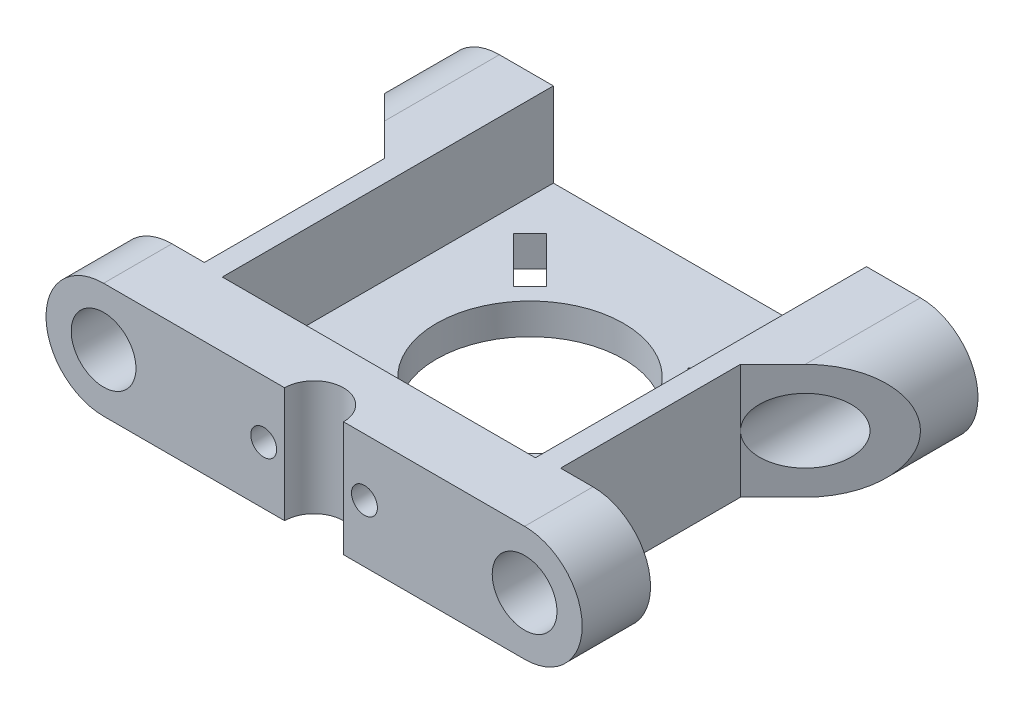
SolidWorks part; units mm, degrees
ref_plane "Piano frontale" through (0, 0, 0) normal (0, 0, 1) x (1, 0, 0)
ref_plane "Piano superiore" through (0, 0, 0) normal (0, 1, 0) x (1, 0, 0)
ref_plane "Piano destro" through (0, 0, 0) normal (1, 0, 0) x (0, 0, -1)
sketch "Schizzo1" plane through (0, 0, 0) normal (0, 0, 1) x (1, 0, 0)
  line L0 (-29.25, 0) -> (29.25, 0) construction
  line L1 (-29.25, -8) -> (29.25, -8)
  line L2 (0, 8) -> (0, -8) construction
  line L3 (-29.25, 8) -> (29.25, 8)
  arc A0 (-29.25, 8) -> (-29.25, -8) centre (-29.25, 0) ccw
  circle A1 centre (-29.25, 0) radius 4.5
  circle A2 centre (29.25, 0) radius 4.5
  arc A3 (29.25, 8) -> (29.25, -8) centre (29.25, 0) cw
  point P4 (0, 0)
  dimension "D2" = 16
  dimension "D3" = 9
  dimension "D1" = 29.25
extrude "Base" add sketch "Schizzo1" along normal mid plane 55
sketch "Schizzo3" plane through (0, 8, 0) normal (0, 1, 0) x (1, 0, 0)
  line L0 (13, 2.5) -> (-13, 2.5) construction
  line L1 (16.1927, 20.9555) -> (12.0915, 12.3288) construction
  line L2 (9.8288, 14.5915) -> (18.4555, 18.6927) construction
  line L3 (12.0915, 12.3288) -> (18.4555, 18.6927)
  line L4 (16.1927, 20.9555) -> (18.4555, 18.6927)
  line L5 (9.8288, 14.5915) -> (12.0915, 12.3288)
  line L6 (9.8288, 14.5915) -> (16.1927, 20.9555)
  line L7 (9.8288, -9.5915) -> (18.4555, -13.6927) construction
  line L8 (37.25, -27.5) -> (37.25, -18)
  line L9 (37.25, -27.5) -> (37.25, 27.5) construction
  line L10 (37.25, -18) -> (24.75, -18)
  line L11 (24.75, -18) -> (24.75, 7)
  line L12 (24.75, -27.5) -> (24.75, -18) construction
  line L13 (24.75, 7) -> (37.25, 19.5)
  line L14 (37.25, 19.5) -> (37.25, -18)
  line L15 (16.1927, -15.9555) -> (12.0915, -7.3288) construction
  line L16 (0, 27.5) -> (0, -27.5) construction
  line L17 (29.25, 27.5) -> (-29.25, 27.5) construction
  line L18 (29.25, -27.5) -> (-29.25, -27.5) construction
  line L19 (-37.25, 19.5) -> (-37.25, -18)
  line L20 (-24.75, 7) -> (-37.25, 19.5)
  line L21 (-24.75, -18) -> (-24.75, 7)
  line L22 (-37.25, -18) -> (-24.75, -18)
  line L23 (-37.25, -27.5) -> (-37.25, -18)
  line L24 (0, 2.5) -> (-14.1421, 16.6421) construction
  line L25 (-9.8288, 14.5915) -> (-16.1927, 20.9555)
  line L26 (-9.8288, 14.5915) -> (-12.0915, 12.3288)
  line L27 (-16.1927, 20.9555) -> (-18.4555, 18.6927)
  line L28 (-12.0915, 12.3288) -> (-18.4555, 18.6927)
  line L29 (-9.8288, 14.5915) -> (-18.4555, 18.6927) construction
  line L30 (-16.1927, 20.9555) -> (-12.0915, 12.3288) construction
  line L31 (9.8288, -9.5915) -> (16.1927, -15.9555)
  line L32 (9.8288, -9.5915) -> (12.0915, -7.3288)
  line L33 (16.1927, -15.9555) -> (18.4555, -13.6927)
  line L34 (12.0915, -7.3288) -> (18.4555, -13.6927)
  line L35 (-16.1927, -15.9555) -> (-12.0915, -7.3288) construction
  line L36 (-9.8288, -9.5915) -> (-18.4555, -13.6927) construction
  line L37 (-12.0915, -7.3288) -> (-18.4555, -13.6927)
  line L38 (-16.1927, -15.9555) -> (-18.4555, -13.6927)
  line L39 (-9.8288, -9.5915) -> (-12.0915, -7.3288)
  line L40 (-9.8288, -9.5915) -> (-16.1927, -15.9555)
  line L41 (24.75, -27.5) -> (33.75, -27.5) construction
  line L42 (24.75, -27.5) -> (33.75, -27.5)
  line L43 (4.09, -27.5) -> (-4.09, -27.5)
  circle A0 centre (0, 2.5) radius 13
  arc A1 (-4.09, -27.5) -> (4.09, -27.5) centre (0, -27.5) cw
  point P26 (0, 2.5)
  line M14 (-29.25, -27.5) -> (29.25, -27.5)
  line M15 (29.25, -27.5) -> (29.25, 27.5)
  dimension "D4" = 26
  dimension "D1" = 9.5
  dimension "D2" = 25
  dimension "D3" = 135
  dimension "D5" = 45
  dimension "D6" = 3.2
  dimension "D7" = 9
  dimension "D8" = 15.5
  dimension "D9" = 25
  dimension "D10" = 8.18
extrude "Holes" cut sketch "Schizzo3" against normal through all contours L13 L11 L10 M15 | L14 L13 L10 M15 | A0 | A1 M14 | L3 L4 L6 L5 | L25 L27 L28 L26 | L22 L21 L20 L19 | L40 L38 L37 L39 | L31 L33 L34 L32 region at (0, 8, 25.7642) region at (33.4092, 8, 1.1704) region at (27.0619, 8, 4.344) region at (0, 8, -2.5)
sketch "Schizzo5" plane through (0, 8, 0) normal (0, 1, 0) x (1, 0, 0)
  line L0 (21.75, 27.5) -> (21.75, -18.5)
  line L1 (29.25, 27.5) -> (-29.25, 27.5) construction
  line L2 (21.75, -18.5) -> (-21.75, -18.5)
  line L3 (-21.75, -18.5) -> (-21.75, 27.5)
  line L4 (-21.75, 0) -> (21.75, 0) construction
  line L5 (-24.75, -18) -> (-24.75, 7) construction
  line L6 (29.25, -27.5) -> (4.09, -27.5) construction
  line L7 (21.75, 27.5) -> (-21.75, 27.5)
  point P10 (0, 0)
  dimension "D1" = 3
  dimension "D2" = 9
extrude "Flange" cut sketch "Schizzo5" against normal blind 11.7
sketch "Schizzo6" plane through (0, 0, 27.5) normal (0, 0, 1) x (1, 0, 0)
  line L0 (0, -8) -> (0, 8) construction
  line L3 (4.09, -8) -> (-4.09, -8) construction
  line L4 (4.09, 8) -> (-4.09, 8) construction
  line L5 (-37.25, 0) -> (37.25, 0) construction
  arc A0 (-29.25, 8) -> (-29.25, -8) centre (-29.25, 0) ccw construction
  arc A1 (29.25, -8) -> (29.25, 8) centre (29.25, 0) ccw construction
  circle A2 centre (7, 0) radius 1.8
  circle A3 centre (-7, 0) radius 1.8
  dimension "D1" = 3.6
  dimension "D2" = 7
extrude "Screw holes" cut sketch "Schizzo6" against normal up to next
sketch "Schizzo7" plane through (0, 0, 18.5) normal (0, 0, -1) x (-1, 0, 0)
  line L1 (-3.6, 0) -> (-5.3, 2.9445)
  line L2 (-5.3, 2.9445) -> (-8.7, 2.9445)
  line L3 (-8.7, 2.9445) -> (-10.4, 0)
  line L4 (-10.4, 0) -> (-8.7, -2.9445)
  line L5 (-8.7, -2.9445) -> (-5.3, -2.9445)
  line L6 (-5.3, -2.9445) -> (-3.6, 0)
  line L7 (10.4, 0) -> (8.7, 2.9445)
  line L8 (8.7, 2.9445) -> (5.3, 2.9445)
  line L9 (5.3, 2.9445) -> (3.6, 0)
  line L10 (3.6, 0) -> (5.3, -2.9445)
  line L11 (5.3, -2.9445) -> (8.7, -2.9445)
  line L12 (8.7, -2.9445) -> (10.4, 0)
  circle A0 centre (-7, 0) radius 2.9445 construction
  circle A1 centre (7, 0) radius 1.8 construction
  circle A2 centre (7, 0) radius 1.8
  circle A3 centre (7, 0) radius 2.9445 construction
  dimension "D1" = 6.8
  dimension "D2" = 6.8
extrude "Nut holes" cut sketch "Schizzo7" against normal blind 2.4
ref_axis "Motor axis" through (0, -8, -2.5) along (0, 1, 0)
ref_axis "Bar1 clamp" through (-29.25, 0, -7) along (0, 0, -1)
ref_axis "Bar 2 clamp" through (29.25, 0, -7) along (0, 0, -1)
